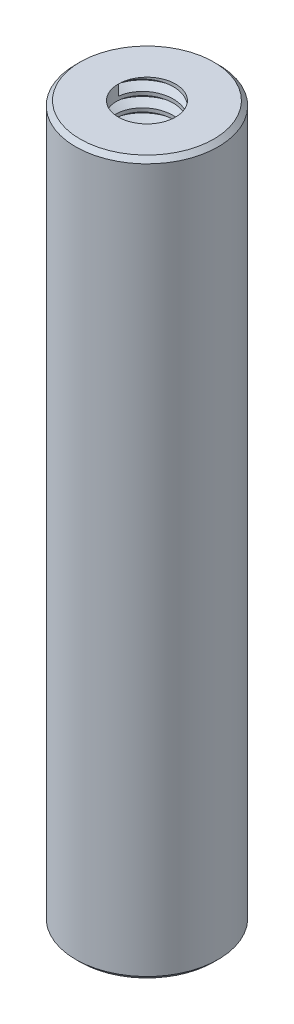
SolidWorks part; units mm, degrees
material "6061-T6 (SS)"
ref_plane "Alzado" through (0, 0, 0) normal (0, 0, 1) x (1, 0, 0)
ref_plane "Planta" through (0, 0, 0) normal (0, 1, 0) x (1, 0, 0)
ref_plane "Vista lateral" through (0, 0, 0) normal (1, 0, 0) x (0, 0, -1)
sketch "Croquis2" plane through (0, 0, 0) normal (0, 1, 0) x (1, 0, 0)
  circle A0 centre (0, 0) radius 6.35
  dimension "D1" = 12.7
extrude "Saliente-Extruir1" add sketch "Croquis2" along normal mid plane 63.5
chamfer "Chaflán1" distance 0.3969 angle 45 2 edges at (0, -31.75, 6.35) (0, 31.75, 6.35)
sketch "Croquis3" plane through (0, 0, 0) normal (0, 1, 0) x (1, 0, 0)
  circle A0 centre (0, 0) radius 2.5527
  dimension "D1" = 5.1054
extrude "Tap Hole 1" cut sketch "Croquis3" against normal blind 19.05 from surface starting at face at (0, 31.75, 5.9531)
extrude "Tap Hole 2" cut sketch "Croquis3<2>" along normal blind 19.05 from surface starting at face at (0, -31.75, 5.9531)
sketch "Croquis3<2>" plane through (0, 0, 0) normal (0, 1, 0) x (1, 0, 0) same geometry as "Croquis3"
sketch "Croquis4" plane through (0, 0, 0) normal (0, 1, 0) x (1, 0, 0)
  circle A0 centre (0, 0) radius 3.2639
  dimension "D1" = 6.5278
extrude "Clearance Hole" [suppressed] cut sketch "Croquis4" against normal through all both and the other way through all
thread "Rosca1" pitch 1.27 method cut profile "Perfil de rosca1" start angle 0, offset 0, length 0, pitch 1.27, diameter 5.1054
ref_plane "Plano1" through (-2.5527, 31.75, 0) normal (0, 0, 1) x (-1, 0, 0)
sketch "Perfil de rosca1" plane through (-2.5527, 31.75, 0) normal (0, 0, 1) x (-1, 0, 0)
  line L0 (0, 0) -> (0, 1.27) construction
  line L1 (0, 0) -> (0.6874, 0.3969)
  line L2 (0.6874, 0.3969) -> (0.6874, 0.5556)
  line L3 (0.6874, 0.5556) -> (0, 0.9525)
  line L4 (0.6874, 0.4762) -> (0, 0.4762) construction
  line L11 (0, 0) -> (0, 0.9525)
  point P2 (0, 0)
  dimension "Pitch" = 1.27
  dimension "Profile_Angle" = 60
  dimension "Profile_Land" = 0.1588
  dimension "Profile_Height" = 0.6874
thread "Rosca2" pitch 1.27 method cut profile "Perfil de rosca2" start angle 0, offset 0, length 0, pitch 1.27, diameter 5.1054
ref_plane "Plano2" through (2.5527, -31.75, 0) normal (0, 0, 1) x (1, 0, 0)
sketch "Perfil de rosca2" plane through (2.5527, -31.75, 0) normal (0, 0, 1) x (1, 0, 0)
  line L0 (0, 0) -> (0, 1.27) construction
  line L1 (0, 0) -> (0.6874, 0.3969)
  line L2 (0.6874, 0.3969) -> (0.6874, 0.5556)
  line L3 (0.6874, 0.5556) -> (0, 0.9525)
  line L4 (0.6874, 0.4762) -> (0, 0.4762) construction
  line L11 (0, 0) -> (0, 0.9525)
  point P2 (0, 0)
  dimension "Pitch" = 1.27
  dimension "Profile_Angle" = 60
  dimension "Profile_Land" = 0.1588
  dimension "Profile_Height" = 0.6874
equation "\"OD\"= 0.5pulgadas"
equation "\"Largo\" = 2.5pulgadas"
equation "\"Tap Hole\"= IIF ( \"OD\" = 0.375pulgadas , 0.1590pulgadas , 0.201pulgadas )"
equation "\"Spacer Hole\"= IIF ( \"OD\" = 0.375pulgadas , 0.196pulgadas , 0.257pulgadas )"
equation "\"D1@Croquis2\"=\"OD\""
equation "\"D1@Saliente-Extruir1\"=\"Largo\""
equation "\"D1@Croquis3\"=\"Tap Hole\""
equation "\"D1@Croquis4\"=\"Spacer Hole\""
